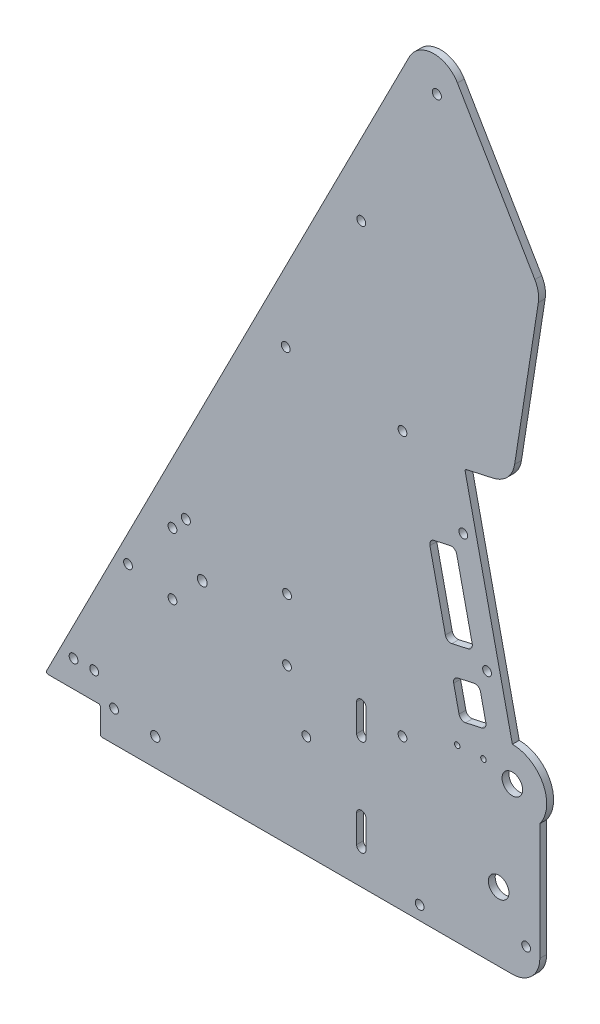
SolidWorks part; units mm, degrees
other "Markup1"
sketch "Sketch5"
ref_plane "Front Plane" through (0, 0, 0) normal (0, 0, 1) x (1, 0, 0)
ref_plane "Top Plane" through (0, 0, 0) normal (0, 1, 0) x (1, 0, 0)
ref_plane "Right Plane" through (0, 0, 0) normal (1, 0, 0) x (0, 0, -1)
sketch "Sketch1" plane through (0, 0, 0) normal (0, 0, 1) x (1, 0, 0)
  line L1 (228.6, -12.7) -> (228.6, 53.975)
  line L2 (178.7547, 351.4131) -> (0, 0)
  line L3 (228.6, 266.7) -> (178.7547, 351.4131)
  line L5 (0, 0) -> (25.4, 0)
  line L6 (25.4, 0) -> (25.4, -12.7)
  line L7 (25.4, -12.7) -> (228.6, -12.7)
  line L9 (215.9, 79.375) -> (193.9097, 178.5667)
  line L10 (193.9097, 178.5667) -> (215.6079, 183.377)
  line L11 (215.6079, 183.377) -> (228.6, 266.7)
  arc A0 (228.6, 53.975) -> (215.9, 79.375) centre (215.9, 63.5) ccw
  dimension "D7" = 12.7
  dimension "D8" = 76.2
  dimension "D10" = 31.75
  dimension "D2" = 279.4
  dimension "D3" = 25.4
  dimension "D4" = 215.9
  dimension "D5" = 394.2644
  dimension "D6" = 203.2
  dimension "D9" = 63.039
  dimension "D11" = 101.6
  dimension "D12" = 12.5
  dimension "D13" = 22.225
extrude "Boss-Extrude1" add sketch "Sketch1" along normal blind 3.175
sketch "Sketch2" plane through (0, 0, 3.175) normal (0, 0, 1) x (1, 0, 0)
  line L0 (178.7547, 351.4131) -> (0, 0) construction
  line L1 (25.4, -12.7) -> (228.6, -12.7) construction
  line L2 (215.9, 79.375) -> (193.9097, 178.5667) construction
  line L3 (193.9097, 178.5667) -> (215.6079, 183.377) construction
  line L4 (215.9, 79.375) -> (193.9097, 178.5667) construction
  line L5 (64.9432, 94.0578) -> (72.5445, 73.1732) construction
  line L6 (64.9432, 94.0578) -> (103.3734, 94.0578) construction
  line L10 (228.6, -12.7) -> (228.6, 53.975) construction
  circle A0 centre (64.9432, 94.0578) radius 2.0955
  circle A1 centre (180.975, 322.1643) radius 2.0955
  circle A2 centre (72.5445, 73.1732) radius 2.286
  circle A3 centre (193.2078, 152.3944) radius 2.032
  circle A4 centre (215.9, 63.5) radius 4.7625
  circle A7 centre (173.0375, -6.35) radius 2.032
  circle A8 centre (204.203, 102.7985) radius 2.032
  circle A26 centre (209.55, 19.05) radius 4.7625
  arc A30 (228.6, 53.975) -> (215.9, 79.375) centre (215.9, 63.5) ccw construction
  circle A31 centre (165.1, 179.3875) radius 2.032
  circle A35 centre (111.724, 87.4607) radius 2.032
  circle A36 centre (111.724, 58.8857) radius 2.032
  circle A37 centre (58.765, 58.8857) radius 2.032
  circle A38 centre (58.765, 87.4607) radius 2.032
  circle A39 centre (111.724, 58.8857) radius 1.905 construction
  circle A42 centre (111.724, 87.4607) radius 1.905 construction
  circle A43 centre (58.765, 58.8857) radius 1.905 construction
  circle A44 centre (58.765, 87.4607) radius 1.905 construction
  dimension "D3" = 4.191
  dimension "D5" = 4.191
  dimension "D9" = 4.572
  dimension "D20" = 9.525
  dimension "D23" = 9.525
  dimension "D18" = 4.064
  dimension "D26" = 4.064
  dimension "D14" = 4.064
  dimension "D10" = 4.064
  dimension "D2" = 15.24
  dimension "D6" = 15.24
  dimension "D7" = 22.225
  dimension "D21" = 44.45
  dimension "D22" = 6.35
  dimension "D19" = 160.3375
  dimension "D24" = 44.45
  dimension "D25" = 6.35
  dimension "D27" = 25.4
  dimension "D28" = 50.8
  dimension "D29" = 6.35
  dimension "D17" = 6.35
  dimension "D33" = 55.5625
  dimension "D15" = 114.3
  dimension "D4" = 180.975
  dimension "D8" = 70
extrude "Cut-Extrude1" cut sketch "Sketch2" against normal through all
sketch "Sketch7" plane through (0, 0, 3.175) normal (0, 0, 1) x (1, 0, 0)
  line L0 (146.05, 3.175) -> (146.05, 15.875) construction
  line L1 (143.891, 3.175) -> (143.891, 15.875)
  line L2 (148.209, 3.175) -> (148.209, 15.875)
  line L3 (146.05, 47.625) -> (146.05, 60.325) construction
  line L4 (143.891, 47.625) -> (143.891, 60.325)
  line L5 (148.209, 47.625) -> (148.209, 60.325)
  line L6 (25.4, -12.7) -> (228.6, -12.7) construction
  line L12 (228.6, -12.7) -> (228.6, 53.975) construction
  line L13 (25.4, -12.7) -> (228.6, -12.7) construction
  arc A0 (143.891, 3.175) -> (148.209, 3.175) centre (146.05, 3.175) ccw
  arc A1 (148.209, 15.875) -> (143.891, 15.875) centre (146.05, 15.875) ccw
  arc A2 (143.891, 47.625) -> (148.209, 47.625) centre (146.05, 47.625) ccw
  arc A3 (148.209, 60.325) -> (143.891, 60.325) centre (146.05, 60.325) ccw
  circle A8 centre (50.8, 0) radius 2.159
  point P2 (146.05, 9.525)
  point P9 (146.05, 53.975)
  dimension "D1" = 4.318
  dimension "D5" = 4.318
  dimension "D2" = 12.7
  dimension "D3" = 12.7
  dimension "D4" = 44.45
  dimension "D6" = 95.25
  dimension "D7" = 82.55
  dimension "D8" = 15.875
  dimension "D9" = 12.7
extrude "Cut-Extrude2" cut sketch "Sketch7" against normal through all
sketch "Sketch10" plane through (0, 0, 3.175) normal (0, 0, 1) x (1, 0, 0)
  circle A0 centre (120.65, 34.925) radius 2.032
  circle A1 centre (165.1, 57.15) radius 2.032
  circle A2 centre (13.0465, 12.3347) radius 2.032
  circle A3 centre (22.5715, 12.3347) radius 2.032
  circle A4 centre (38.2114, 62.6398) radius 2.032
  dimension "D1" = 4.064
  dimension "D3" = 34.925
  dimension "D2" = 120.65
  dimension "D4" = 63.5
  dimension "D5" = 69.85
extrude "Cut-Extrude3" cut sketch "Sketch10" against normal up to next
fillet "Fillet1" radius 12.7 4 edges at (228.6, -12.7, 1.5875) (178.7547, 351.4131, 1.5875) (215.6079, 183.377, 1.5875) (228.6, 266.7, 1.5875)
fillet "Fillet2" radius 0.7937 4 edges at (25.4, -12.7, 1.5875) (25.4, 0, 1.5875) (193.9097, 178.5667, 1.5875) (0, 0, 1.5875)
sketch "Sketch12" plane through (0, 0, 3.175) normal (0, 0, 1) x (1, 0, 0)
  circle A0 centre (31.75, 1.5875) radius 2.032
  circle A1 centre (173.0375, -6.35) radius 2.032
  circle A2 centre (222.25, 1.5875) radius 2.032
  dimension "D1" = 4.064
extrude "Cut-Extrude5" cut sketch "Sketch12" against normal through all
sketch "Sketch13" plane through (0, 0, 3.175) normal (0, 0, 1) x (1, 0, 0)
  line L1 (228.6, 0) -> (228.6, 53.975) construction
  line L2 (1.2943, 0) -> (24.6062, 0) construction
  line L3 (26.1937, -12.7) -> (215.9, -12.7) construction
  circle A0 centre (111.125, 186.055) radius 2.032
  circle A1 centre (146.05, 254) radius 2.032
  dimension "D2" = 4.064
  dimension "D5" = 4.064
  dimension "D1" = 198.755
  dimension "D3" = 82.55
  dimension "D4" = 254
  dimension "D6" = 117.475
extrude "Cut-Extrude6" cut sketch "Sketch13" against normal through all
sketch "Sketch14" plane through (0, 0, 3.175) normal (0, 0, 1) x (1, 0, 0)
  line L0 (177.2237, 142.3466) -> (189.6226, 145.0954)
  line L1 (189.6226, 145.0954) -> (197.869, 107.8985)
  line L2 (197.869, 107.8985) -> (185.47, 105.1497)
  line L3 (185.47, 105.1497) -> (177.2237, 142.3466)
  line L4 (187.1428, 144.5456) -> (179.7035, 142.8963) construction
  line L5 (188.2188, 92.7508) -> (200.6178, 95.4995)
  line L6 (188.2188, 92.7508) -> (191.7922, 76.6321)
  line L7 (191.7922, 76.6321) -> (204.1912, 79.3809)
  line L8 (200.6178, 95.4995) -> (204.1912, 79.3809)
  line L11 (197.3192, 110.3783) -> (190.1724, 142.6156) construction
  line L12 (177.7734, 139.8668) -> (184.9203, 107.6295) construction
  line L13 (187.9498, 105.6995) -> (195.3892, 107.3487) construction
  line L14 (203.6414, 81.8607) -> (201.1675, 93.0197) construction
  line L15 (194.272, 77.1819) -> (201.7114, 78.8311) construction
  line L16 (188.7686, 90.271) -> (191.2425, 79.1119) construction
  line L17 (198.138, 94.9498) -> (190.6986, 93.3005) construction
  circle A0 centre (190.4268, 66.2609) radius 1.27
  circle A1 centre (202.5335, 66.7895) radius 1.27
  circle A2 centre (190.4268, 66.2609) radius 1.27 construction
  circle A3 centre (202.5335, 66.7895) radius 1.27 construction
  point P8 (152.4, 88.9)
extrude "Cut-Extrude7" cut sketch "Sketch14" against normal through all both and the other way through all
fillet "Fillet3" radius 2.54 8 edges at (200.6178, 95.4995, 1.5875) (188.2188, 92.7508, 1.5875) (191.7922, 76.6321, 1.5875) (204.1912, 79.3809, 1.5875) (197.869, 107.8985, 1.5875) (185.47, 105.1497, 1.5875) (177.2237, 142.3466, 1.5875) (189.6226, 145.0954, 1.5875)
equation "\"D6@Sketch2\"=\"D2@Sketch2\""
